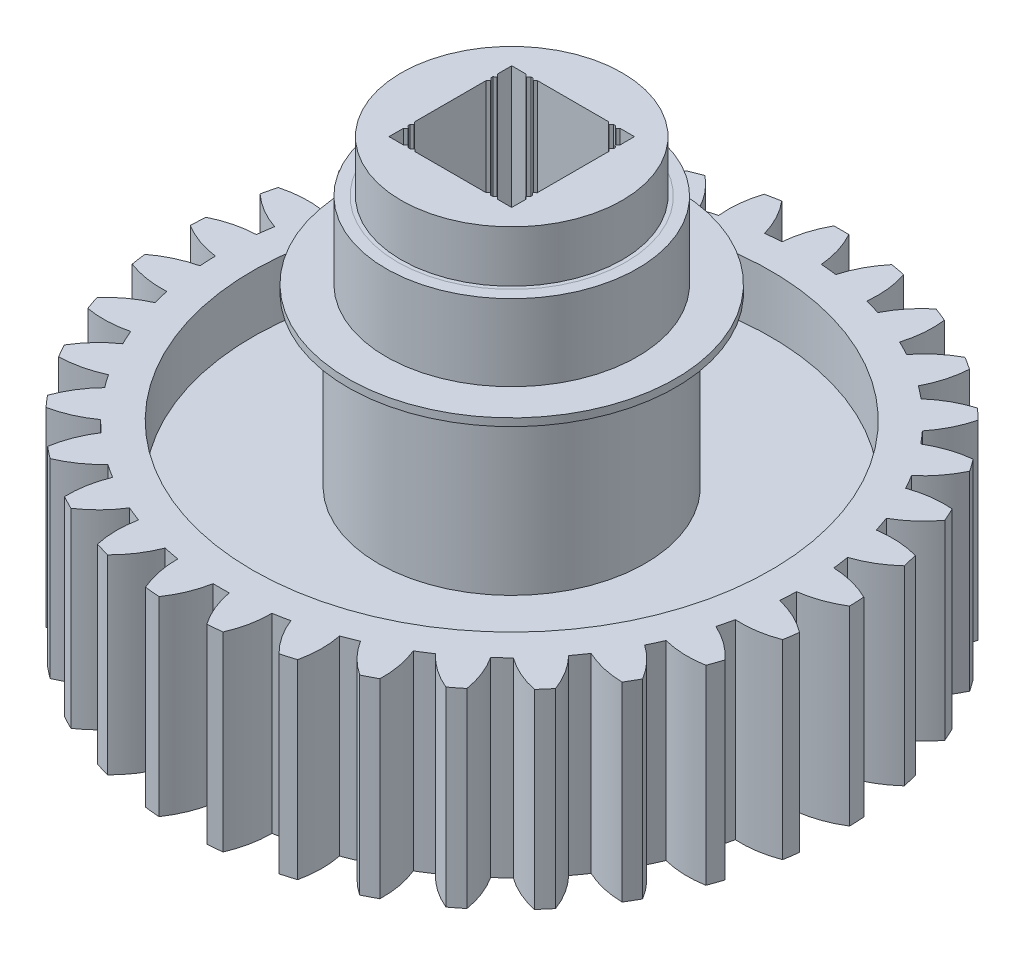
SolidWorks part; units mm, degrees
material "ABS PC"
ref_plane "Front Plane" through (0, 0, 0) normal (0, 0, 1) x (1, 0, 0)
ref_plane "Top Plane" through (0, 0, 0) normal (0, 1, 0) x (1, 0, 0)
ref_plane "Right Plane" through (0, 0, 0) normal (1, 0, 0) x (0, 0, -1)
sketch "Sketch1" plane through (0, 0, 0) normal (0, 0, 1) x (1, 0, 0)
  line L0 (0, 12.8318) -> (0, 0) construction
  line L1 (-2.3, 5.1) -> (-0.3, 5.1)
  line L2 (-2.3, 5.1) -> (-2.3, 2.3)
  line L3 (-2.3, 2.3) -> (-5, 2.3)
  line L4 (-5, 2.3) -> (-5, -1.1)
  line L5 (-5, -1.1) -> (-6, -1.1)
  line L6 (-6, -1.1) -> (-6, 1.5)
  line L7 (-6, 1.5) -> (-6.8, 1.5)
  line L8 (-6.8, 1.5) -> (-6.8, 0)
  line L9 (-6.8, 0) -> (-7.57, 0)
  line L10 (-7.57, 0) -> (-7.57, 5)
  line L11 (-7.57, 5) -> (-6.8, 5)
  line L12 (-6.8, 5) -> (-6.8, 3.5)
  line L13 (-6.8, 3.5) -> (-3.5, 3.5)
  line L14 (-3.5, 3.5) -> (-3.5, 7.9)
  line L15 (-3.5, 7.9) -> (-3, 7.9)
  line L16 (-3, 7.9) -> (-3, 10.1)
  line L17 (-3, 10.1) -> (-2.9, 10.1)
  line L18 (-2.9, 10.1) -> (-2.9, 11.45)
  line L19 (-2.9, 11.45) -> (-0.3, 11.45)
  line L22 (-0.3, 11.45) -> (-0.3, 5.1)
  point P23 (0, 0)
  dimension "D2" = 0.6
  dimension "D3" = 2.8
  dimension "D4" = 2.7
  dimension "D5" = 3.4
  dimension "D6" = 2.6
  dimension "D7" = 1
  dimension "D8" = 0.8
  dimension "D9" = 1.5
  dimension "D10" = 0.77
  dimension "D11" = 5
  dimension "D12" = 3.3
  dimension "D13" = 1.5
  dimension "D14" = 0.5
  dimension "D15" = 4.4
  dimension "D16" = 0.1
  dimension "D17" = 2.2
  dimension "D18" = 15.14
  dimension "D19" = 1.35
revolve "Revolve1" add sketch "Sketch1" angle 360 about L0
sketch "Sketch2" plane through (0, 11.45, 0) normal (0, 1, 0) x (1, 0, 0)
  line L0 (0, -1.8094) -> (0, 2.3037) construction
  line L1 (-1.61, 1.61) -> (1.61, 1.61)
  line L2 (-1.61, 1.61) -> (-1.61, -1.61)
  line L3 (-1.61, -1.61) -> (1.61, -1.61)
  line L4 (1.61, 1.61) -> (1.61, -1.61)
  point P6 (0, 0)
  dimension "D1" = 3.22
  dimension "D2" = 1.61
  dimension "D3" = 3.22
extrude "Cut-Extrude1" cut sketch "Sketch2" against normal blind 5.85
sketch "Sketch3" plane through (0, 2.3, 0) normal (0, -1, 0) x (1, 0, 0)
  line L0 (0, -5) -> (0, 4.809) construction
  line L1 (3, 3.3226) -> (3, 4)
  line L2 (-3, -4) -> (-3, -3.3226)
  line L3 (-3, 3.3226) -> (-3, 4)
  line L4 (0, -4.4) -> (0, -2.4) construction
  line L5 (3, -4) -> (3, -3.3226)
  line L6 (-2.6971, 0) -> (3.3961, 0) construction
  circle A0 centre (0, 0) radius 5 construction
  arc A1 (3.2308, 2.6837) -> (3.2308, -2.6837) centre (0, 0) cw
  arc A2 (3, 4) -> (3, -4) centre (0, 0) cw
  arc A3 (3.2308, 2.6837) -> (3, 3.3226) centre (4, 3.3226) cw
  arc A4 (3, -3.3226) -> (3.2308, -2.6837) centre (4, -3.3226) cw
  circle A5 centre (0, -3.4) radius 1
  arc A6 (-3, -3.3226) -> (-3.2308, -2.6837) centre (-4, -3.3226) ccw
  arc A7 (-3.2308, 2.6837) -> (-3, 3.3226) centre (-4, 3.3226) ccw
  arc A8 (-3, 4) -> (-3, -4) centre (0, 0) ccw
  arc A9 (-3.2308, 2.6837) -> (-3.2308, -2.6837) centre (0, 0) ccw
  circle A10 centre (0, 3.4) radius 1
  point P12 (0, 0)
  dimension "D1" = 1
  dimension "D3" = 4.2
  dimension "D4" = 5
  dimension "D5" = 1
  dimension "D6" = 1
  dimension "D2" = 3.4
  dimension "D7" = 0.6774
  dimension "D8" = 0.6774
  dimension "D9" = 8
  dimension "D10" = 3
  dimension "D11" = 0.2308
  dimension "D12" = 0.2308
extrude "Extrude1" add sketch "Sketch3" along normal blind 1.2
sketch "Sketch4" plane through (0, 0, 0) normal (0, -1, 0) x (1, 0, 0)
  circle A4 centre (0, 0) radius 7.57 construction
  arc A5 (1.2209, 7.4709) -> (-1.2235, 7.4705) centre (0, 0) ccw
  arc A7 (1.2209, 7.4709) -> (1.0032, 8.5916) centre (-1.388, 7.5456) ccw
  arc A8 (1.0032, 8.5916) -> (0.6266, 8.6273) centre (0, 0) ccw
  arc A9 (-1.0038, 8.5916) -> (-1.2235, 7.4705) centre (1.3856, 7.5413) ccw
  arc A10 (-0.6266, 8.6273) -> (-1.0038, 8.5916) centre (0, 0) ccw
  arc A11 (-0.2109, 7.6221) -> (-0.6266, 8.6273) centre (-2.7777, 7.1491) ccw
  arc A12 (0.2109, 7.6221) -> (-0.2109, 7.6221) centre (0, 0) ccw
  arc A13 (0.6266, 8.6273) -> (0.2109, 7.6221) centre (2.7777, 7.1491) ccw
  point P13 (0, 0)
  dimension "D1" = 2.61
  dimension "D2" = 2.61
  dimension "D3" = 2.61
  dimension "D4" = 2.61
  dimension "D5" = 8.65
  dimension "D6" = 8.65
  dimension "D7" = 7.625
  dimension "D8" = 1.1211
  dimension "D10" = 1.0125
  dimension "D11" = 1.01
  dimension "D12" = 0.3788
  dimension "D13" = 0.3782
  dimension "D14" = 1.0052
  dimension "D15" = 1.0052
  dimension "D16" = 7.6221
extrude "Extrude2" add sketch "Sketch4" against normal up to surface (5 mm away) up to face at (0, 5, 7.57)
pattern_circular "CirPattern1" count 33 over 360 about axis through (0, 7.7061, 0) along (0, -1, 0) of "Extrude2"
sketch "Sketch5" plane through (0, 11.45, 0) normal (0, 1, 0) x (-1, 0, 0)
  line L0 (-1.61, 0.941) -> (-1.62, 0.941)
  line L1 (-1.62, 0.941) -> (-1.62, 1.23)
  line L2 (0, 0) -> (-2.4566, 0) construction
  line L3 (-1.61, 1.23) -> (-1.62, 1.23)
  line L4 (1.61, 1.61) -> (-1.61, 1.61) construction
  line L5 (-1.2348, 1.61) -> (-1.1803, 1.5553)
  line L6 (-1.1623, 1.5553) -> (-1.1078, 1.61)
  line L7 (-1.1078, 1.61) -> (-1.057, 1.61)
  line L8 (-1.057, 1.61) -> (-1.0025, 1.5553)
  line L9 (-0.9845, 1.5553) -> (-0.93, 1.61)
  line L10 (-0.93, 1.61) -> (-0.93, 1.6189)
  line L11 (-0.93, 1.6189) -> (-1.2348, 1.6189)
  line L12 (-1.2348, 1.6189) -> (-1.2348, 1.61)
  line L13 (0, 0) -> (0, 2.0737) construction
  line L14 (1.2348, 1.6189) -> (1.2348, 1.61)
  line L15 (0.93, 1.6189) -> (1.2348, 1.6189)
  line L16 (0.93, 1.61) -> (0.93, 1.6189)
  line L17 (0.9845, 1.5553) -> (0.93, 1.61)
  line L18 (1.057, 1.61) -> (1.0025, 1.5553)
  line L19 (1.1078, 1.61) -> (1.057, 1.61)
  line L20 (1.1623, 1.5553) -> (1.1078, 1.61)
  line L21 (1.2348, 1.61) -> (1.1803, 1.5553)
  line L22 (-1.61, 1.61) -> (-1.61, -1.61) construction
  line L23 (-1.5476, -1.18) -> (-1.61, -1.23)
  line L24 (-1.61, -1.1144) -> (-1.5476, -1.1644)
  line L25 (-1.61, 0.941) -> (-1.5513, 0.9954)
  line L26 (-1.5513, 1.01) -> (-1.61, 1.0644)
  line L27 (-1.61, 1.0644) -> (-1.61, 1.1144)
  line L28 (-1.61, 1.1144) -> (-1.5476, 1.1644)
  line L29 (-1.5476, 1.18) -> (-1.61, 1.23)
  line L30 (-1.61, -1.0644) -> (-1.61, -1.1144)
  line L31 (-1.5513, -1.01) -> (-1.61, -1.0644)
  line L32 (-1.61, -0.941) -> (-1.5513, -0.9954)
  line L33 (-1.61, -1.23) -> (-1.62, -1.23)
  line L34 (-1.62, -0.941) -> (-1.62, -1.23)
  line L35 (-1.61, -0.941) -> (-1.62, -0.941)
  arc A0 (1.0025, 1.5553) -> (0.9845, 1.5553) centre (0.9935, 1.5643) cw
  arc A1 (1.1803, 1.5553) -> (1.1623, 1.5553) centre (1.1713, 1.5643) cw
  arc A2 (-1.1803, 1.5553) -> (-1.1623, 1.5553) centre (-1.1713, 1.5643) ccw
  arc A3 (-1.0025, 1.5553) -> (-0.9845, 1.5553) centre (-0.9935, 1.5643) ccw
  arc A4 (-1.5513, 0.9954) -> (-1.5513, 1.01) centre (-1.5581, 1.0027) ccw
  arc A5 (-1.5476, 1.1644) -> (-1.5476, 1.18) centre (-1.5538, 1.1722) ccw
  arc A6 (-1.5476, -1.1644) -> (-1.5476, -1.18) centre (-1.5538, -1.1722) cw
  arc A7 (-1.5513, -0.9954) -> (-1.5513, -1.01) centre (-1.5581, -1.0027) cw
  dimension "D11" = 0.0127
  dimension "D12" = 0.0127
  dimension "D28" = 0.01
  dimension "D29" = 0.38
  dimension "D19" = 0.01
  dimension "D20" = 0.01
  dimension "D1" = 0.3048
  dimension "D2" = 0.0508
  dimension "D3" = 0.0547
  dimension "D4" = 0.0547
  dimension "D5" = 0.0772
  dimension "D6" = 0.0547
  dimension "D7" = 0.0547
  dimension "D8" = 0.0772
  dimension "D9" = 0.0772
  dimension "D10" = 0.0772
  dimension "D13" = 0.0457
  dimension "D14" = 0.93
  dimension "D15" = 0.3048
  dimension "D16" = 0.018
  dimension "D17" = 0.0089
  dimension "D18" = 0.01
  dimension "D21" = 0.08
  dimension "D22" = 0.08
  dimension "D23" = 0.08
  dimension "D24" = 0.08
  dimension "D25" = 0.05
  dimension "D26" = 0.05
  dimension "D27" = 0.0544
extrude "Extrude3" add sketch "Sketch5" against normal up to vertex (5.85 mm away) up to point (-1.61, 5.6, 1.61)
mirror "Mirror1" about plane through (0, 0, 0) normal (0, 0, 1) of "Extrude3"
mirror "Mirror2" about plane through (0, 0, 0) normal (1, 0, 0) of "Mirror1"
sketch "Sketch8" plane through (0, 0, 0) normal (0, 0, 1) x (1, 0, 0)
  line L0 (3, 10.1) -> (3, 7.9)
  line L1 (3, 7.9) -> (4.3, 7.9)
  line L2 (4.3, 7.9) -> (4.3, 8.1)
  line L3 (4.3, 8.1) -> (3.3, 8.1)
  line L4 (3.3, 8.1) -> (3.3, 10.1)
  line L5 (3.3, 10.1) -> (3, 10.1)
  line L6 (0, 11.45) -> (0, 5.0581) construction
  line L7 (-0.93, 11.45) -> (0.93, 11.45) construction
  dimension "D1" = 0.2
  dimension "D2" = 0.3
  dimension "D3" = 1
revolve "Revolve2" add sketch "Sketch8" angle 360 about L6
sketch "Sketch9" plane through (0, 0, 0) normal (0, 0, 1) x (1, 0, 0)
  line L0 (5, -0.7) -> (5, 1.1)
  line L1 (3, 1.1) -> (5, 1.1) construction
  line L2 (5, 1.1) -> (4.4, 1.1)
  line L4 (4.4, -0.7) -> (4.4, 1.1)
  line L5 (4.4, -0.7) -> (5, -0.7)
  line L6 (0, 2.3) -> (0, -2.147) construction
  line L7 (-1, 2.3) -> (1, 2.3) construction
  dimension "D1" = 1.8
  dimension "D2" = 10
  dimension "D3" = 0.6
revolve "Revolve3" add sketch "Sketch9" angle 360 about L6
chamfer "Chamfer1" distance 0.2 angle 45 1 edges at (0, -0.7, 4.4)
